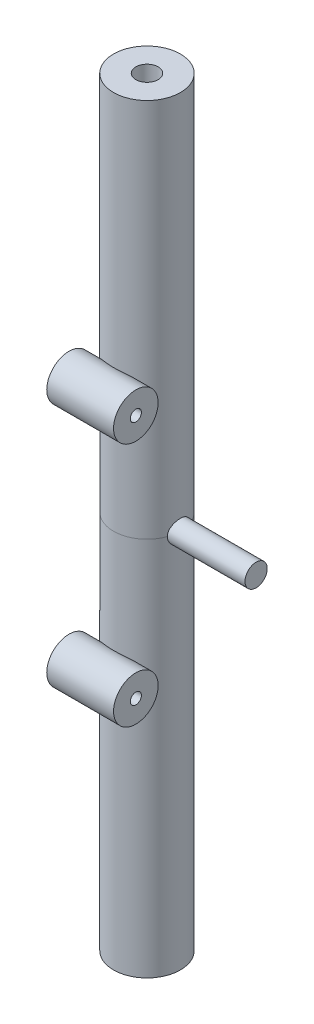
SolidWorks part; units mm, degrees
ref_plane "Płaszczyzna przednia" through (0, 0, 0) normal (0, 0, 1) x (1, 0, 0)
ref_plane "Płaszczyzna górna" through (0, 0, 0) normal (0, 1, 0) x (1, 0, 0)
ref_plane "Płaszczyzna prawa" through (0, 0, 0) normal (1, 0, 0) x (0, 0, -1)
sketch "Szkic1" plane through (0, 0, 0) normal (0, 0, 1) x (1, 0, 0)
  line L0 (10, 0) -> (10, 37.902) construction
  line L1 (0, -123.8759) -> (-20, -123.8759)
  line L2 (0, -123.8759) -> (0, 558.4641)
  line L3 (0, 558.4641) -> (-20, 558.4641)
  line L4 (-20, -123.8759) -> (-20, 558.4641)
  dimension "D1" = 20
  dimension "D2" = 682.34
  dimension "D3" = 10
revolve "Obrót1" add sketch "Szkic1" angle 360 about L0
sketch "Szkic2" plane through (0, 0, 0) normal (0, 0, 1) x (1, 0, 0)
  line L0 (-112.0056, 217.2941) -> (127.5297, 217.2941)
  line L1 (0, -123.8759) -> (0, 558.4641) construction
  point P10 (0, 217.2941)
split line "Linia podziałowa1"
ref_plane "Płaszczyzna1" through (0, 0, 40) normal (0, 0, 1) x (1, 0, 0)
ref_axis "Oś1" through (10, 225.4951, 0) along (0, -1, 0)
sketch "Szkic3" plane through (0, 0, 40) normal (0, 0, 1) x (1, 0, 0)
  line L1 (20, 357.2941) -> (0, 357.2941)
  line L2 (20, 357.2941) -> (20, 297.2941)
  line L3 (20, 297.2941) -> (0, 297.2941)
  line L4 (0, 357.2941) -> (0, 297.2941)
  line L5 (20, 137.2941) -> (0, 137.2941)
  line L6 (20, 137.2941) -> (20, 77.2941)
  line L7 (20, 77.2941) -> (0, 77.2941)
  line L8 (0, 137.2941) -> (0, 77.2941)
  line L9 (10, 225.4951) -> (10, -141.5049) construction
  line L10 (40, 217.2941) -> (-20, 217.2941) construction
  dimension "D1" = 60
  dimension "D2" = 20
  dimension "D3" = 10
  dimension "D4" = 80
  dimension "D5" = 80
sketch "Szkic4" plane through (0, 0, 40) normal (0, 0, 1) x (1, 0, 0)
  line L0 (0, 107.2941) -> (78.1208, 107.2941) construction
  line L1 (-20, 102.2941) -> (40, 102.2941)
  line L2 (-20, 102.2941) -> (-20, 87.2941)
  line L3 (-20, 87.2941) -> (40, 87.2941)
  line L4 (40, 102.2941) -> (40, 87.2941)
  line L5 (20, 137.2941) -> (0, 137.2941) construction
  line L6 (20, 77.2941) -> (0, 77.2941) construction
  line L8 (10, 225.4951) -> (10, -141.5049) construction
  dimension "D1" = 5
  dimension "D2" = 20
  dimension "D3" = 60
  dimension "D4" = 30
revolve "Obrót2" add sketch "Szkic4" angle 360 about L0
ref_plane "Płaszczyzna2" through (0, 217.2941, 0) normal (0, -1, 0) x (-1, 0, 0)
mirror "Lustro1" about plane through (0, 217.2941, 0) normal (0, -1, 0) of "Obrót2"
sketch "Szkic5" plane through (0, 0, 0) normal (1, 0, 0) x (0, 0, -1)
  line L0 (-33, 217.2941) -> (33, 217.2941) construction
  circle A0 centre (0, 217.2941) radius 10
  dimension "D1" = 20
extrude "Dodanie-wyciągnięcie1" add sketch "Szkic5" along normal blind 108 separate body
